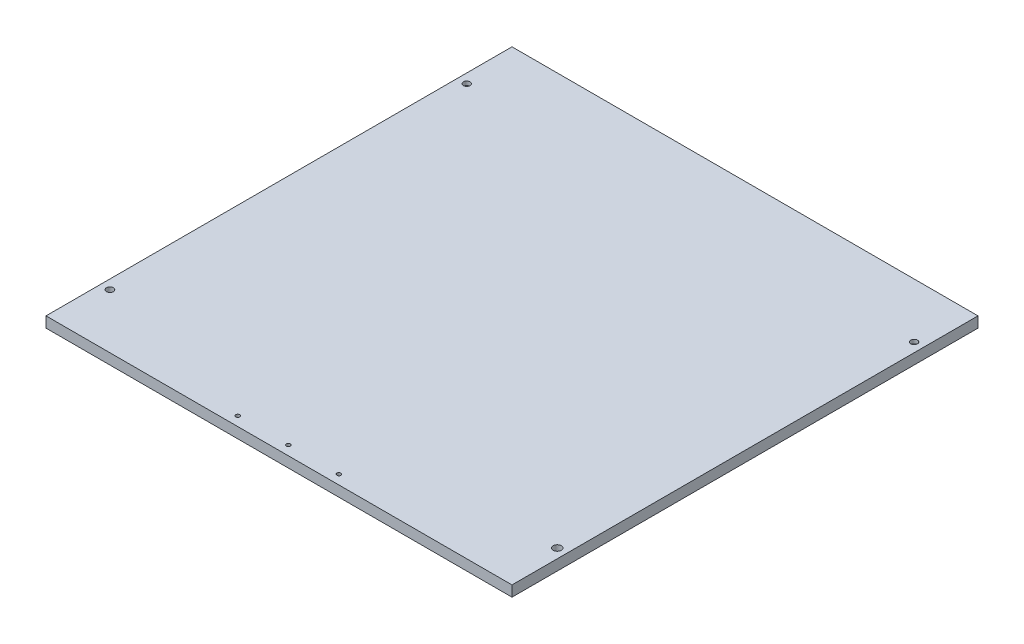
SolidWorks part; units mm, degrees
ref_plane "Front Plane" through (0, 0, 0) normal (0, 0, 1) x (1, 0, 0)
ref_plane "Top Plane" through (0, 0, 0) normal (0, 1, 0) x (1, 0, 0)
ref_plane "Right Plane" through (0, 0, 0) normal (1, 0, 0) x (0, 0, -1)
sketch "PlateSketch2" plane through (0, 0, 0) normal (0, 1, 0) x (1, 0, 0)
  line L1 (0, 0) -> (350, 0)
  line L2 (0, 0) -> (0, 350)
  line L3 (0, 350) -> (350, 350)
  line L4 (350, 0) -> (350, 350)
  circle A0 centre (7, 309) radius 1.5
  circle A1 centre (343, 309) radius 1.5
  circle A2 centre (137, 7) radius 1.5
  circle A3 centre (175, 7) radius 1.5
  circle A4 centre (213, 7) radius 1.5
  circle A5 centre (7, 41) radius 2.5992
  circle A6 centre (343, 41) radius 3.0219
  point P19 (0, 0)
  point P20 (0, 0)
  dimension "D5" = 3
  dimension "D10" = 3
  dimension "D1" = 350
  dimension "D2" = 350
  dimension "D3" = 7
  dimension "D4" = 7
  dimension "D6" = 41
  dimension "D7" = 38
  dimension "D8" = 38
  dimension "D9" = 175
  dimension "D11" = 7
  dimension "D12" = 41
extrude "Boss-Extrude1" add sketch "PlateSketch2" along normal blind 8
sketch "BoreSketch1" plane through (0, 8, 0) normal (0, 1, 0) x (1, 0, 0)
  circle A0 centre (7, 309) radius 2.5
  circle A1 centre (343, 309) radius 2.5
  circle A4 centre (7, 309) radius 1.5 construction
  circle A5 centre (343, 309) radius 1.5 construction
  dimension "D1" = 5
extrude "BoreCut-Extrude1" cut sketch "BoreSketch1" against normal blind 3
equation "\"BuildPlateStandoffHolesDistanceFromLeftOrRightSide\"= 7mm"
equation "\"BuildPlateStandoffHolesDistanceFromBackSide\"= 41mm"
equation "\"BedSpringHoleSize\"= 3mm"
equation "\"BuildPlateWidth\"= 350mm'Spec"
equation "\"BuildPlateLength\"= 350mm'Spec"
equation "\"D5@PlateSketch2\" = \"BedSpringHoleSize\""
equation "\"D10@PlateSketch2\" = \"BedSpringHoleSize\""
equation "\"BuildPlateBoreDiameter\"= 5mm'Spec"
equation "\"D1@BoreSketch1\" = \"BuildPlateBoreDiameter\""
equation "\"BuildPlateBoreDepth\"= 3mm'Spec"
equation "\"D1@BoreCut-Extrude1\" = \"BuildPlateBoreDepth\""
equation "\"BuildPlateDepth\"= 8mm'Spec"
equation "\"D1@Boss-Extrude1\"=\"BuildPlateDepth\""
equation "\"D1@PlateSketch2\"= \"BuildPlateLength\""
equation "\"D2@PlateSketch2\"=\"BuildPlateWidth\""
equation "\"D9@PlateSketch2\"=\"BuildPlateWidth\"/2"
equation "\"BuildPlateFlankingHoles\"= 38mm"
equation "\"D7@PlateSketch2\"=\"BuildPlateFlankingHoles\""
equation "\"D6@PlateSketch2\"=\"BuildPlateStandoffHolesDistanceFromBackSide\""
equation "\"D3@PlateSketch2\"=\"BuildPlateStandoffHolesDistanceFromLeftOrRightSide\""
equation "\"D4@PlateSketch2\"=\"BuildPlateStandoffHolesDistanceFromLeftOrRightSide\""
equation "\"BuildPlateStandoffHolesDistanceFromFront\"= 7mm"
equation "\"D11@PlateSketch2\"=\"BuildPlateStandoffHolesDistanceFromFront\""
equation "\"D12@PlateSketch2\"=\"BuildPlateStandoffHolesDistanceFromBackSide\""
